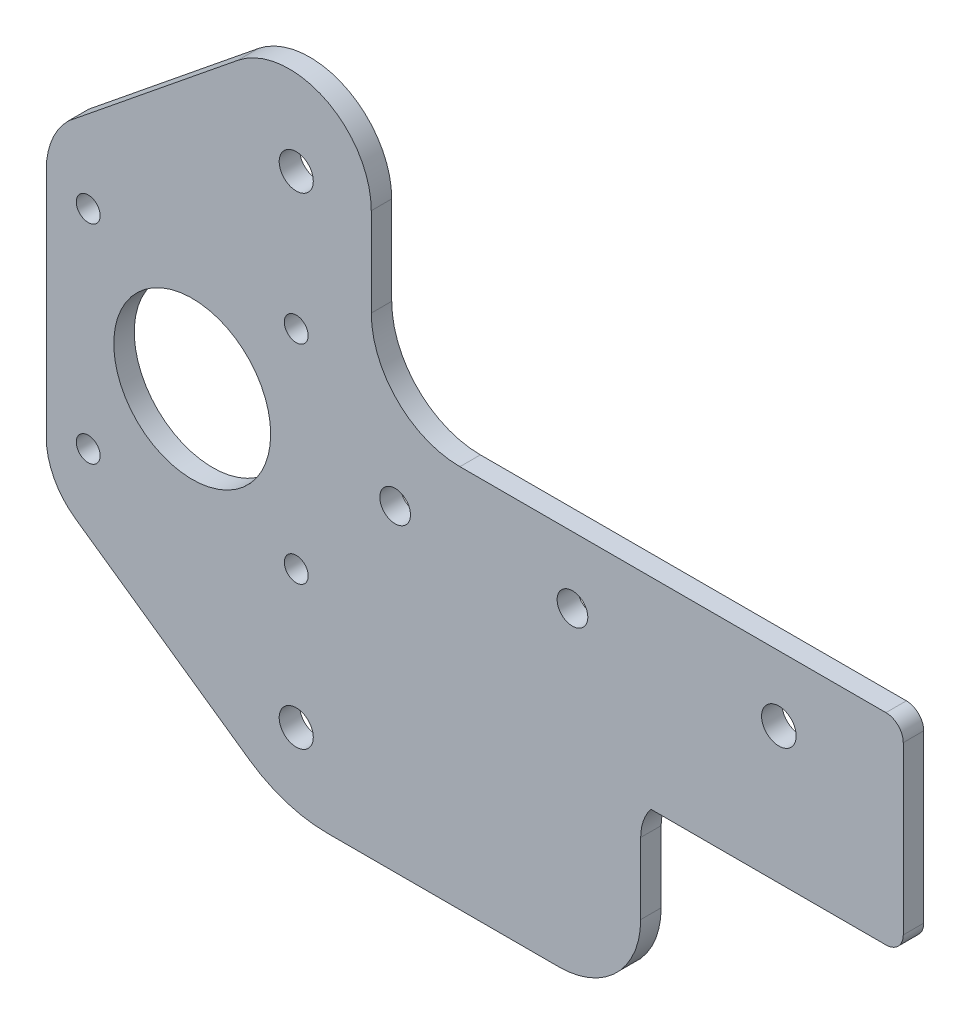
SolidWorks part; units mm, degrees
ref_plane "Front Plane" through (0, 0, 0) normal (0, 0, 1) x (1, 0, 0)
ref_plane "Top Plane" through (0, 0, 0) normal (0, 1, 0) x (1, 0, 0)
ref_plane "Right Plane" through (0, 0, 0) normal (1, 0, 0) x (0, 0, -1)
sketch "Sketch1" plane through (0, 0, 0) normal (0, 0, 1) x (1, 0, 0)
  line L0 (0, 0) -> (0, -29.5)
  line L1 (0, -29.5) -> (-37, -29.5)
  line L2 (0, 0) -> (-65, 0)
  line L3 (-78, 13) -> (-78, 26)
  line L4 (-97.5518, 35.3258) -> (-122.4205, 15.1875)
  line L5 (-125.65, 7.4017) -> (-125.65, -26.5983)
  line L6 (-89, 5.5) -> (-89, -25) construction
  line L7 (-119.5, 5.5) -> (-89, 5.5) construction
  line L8 (-121.3858, -34.7898) -> (-95.8858, -52.6451)
  line L9 (-84.4142, -56.2621) -> (-50.5, -56.2621)
  line L10 (-38.5, -44.2621) -> (-38.5, -33.8301)
  line L11 (-104.25, -9.75) -> (-104.25, 5.5) construction
  line L12 (-104.25, -9.75) -> (-89, -9.75) construction
  arc A0 (-78, 13) -> (-65, 0) centre (-65, 13) ccw
  arc A1 (-78, 26) -> (-97.5518, 35.3258) centre (-90, 26) ccw
  arc A2 (-122.4205, 15.1875) -> (-125.65, 7.4017) centre (-114.65, 7.4017) ccw
  arc A3 (-125.65, -26.5983) -> (-121.3858, -34.7898) centre (-115.65, -26.5983) ccw
  arc A4 (-95.8858, -52.6451) -> (-84.4142, -56.2621) centre (-84.4142, -36.2621) ccw
  arc A5 (-50.5, -56.2621) -> (-38.5, -44.2621) centre (-50.5, -44.2621) ccw
  arc A6 (-37, -29.5) -> (-38.5, -33.8301) centre (-31.5, -33.8301) ccw
  circle A7 centre (-18.237, -9.552) radius 2.54
  circle A8 centre (-48.5, -9.75) radius 2.25
  circle A9 centre (-74.5, -9.75) radius 2.25
  circle A10 centre (-89, 5.5) radius 1.75
  circle A11 centre (-89, 25.5) radius 2.5
  circle A12 centre (-89, -25) radius 1.75
  circle A13 centre (-89, -45.112) radius 2.5
  circle A14 centre (-104.25, -9.75) radius 11.5
  circle A15 centre (-119.5, 5.5) radius 1.75
  circle A16 centre (-119.5, -25) radius 1.75
  point P18 (0, 0)
  dimension "D4" = 24
  dimension "D5" = 26
  dimension "D9" = 56.263
  dimension "D12" = 20
  dimension "D13" = 26
  dimension "D16" = 14
  dimension "D17" = 24
  dimension "D19" = 5.08
  dimension "D20" = 4.5
  dimension "D21" = 4.5
  dimension "D22" = 30.5
  dimension "D23" = 5
  dimension "D24" = 61.7621
  dimension "D25" = 5
  dimension "D26" = 30.5
  dimension "D27" = 23
  dimension "D11" = 3.5
  dimension "D1" = 65
  dimension "D2" = 29.5
  dimension "D3" = 37
  dimension "D6" = 13
  dimension "D7" = 32
  dimension "D8" = 51
  dimension "D10" = 34
  dimension "D14" = 125
  dimension "D15" = 25.5
  dimension "D18" = 1.5
  dimension "D29" = 70.763
  dimension "D30" = 9.75
  dimension "D31" = 9.75
  dimension "D34" = 25.5
  dimension "D37" = 70.612
  dimension "D39" = 35.56
  dimension "D42" = 89
extrude "Boss-Extrude1" add sketch "Sketch1" along normal blind 3
fillet "Fillet2" radius 2.54 2 edges at (0, 0, 1.5) (0, -29.5, 1.5)
